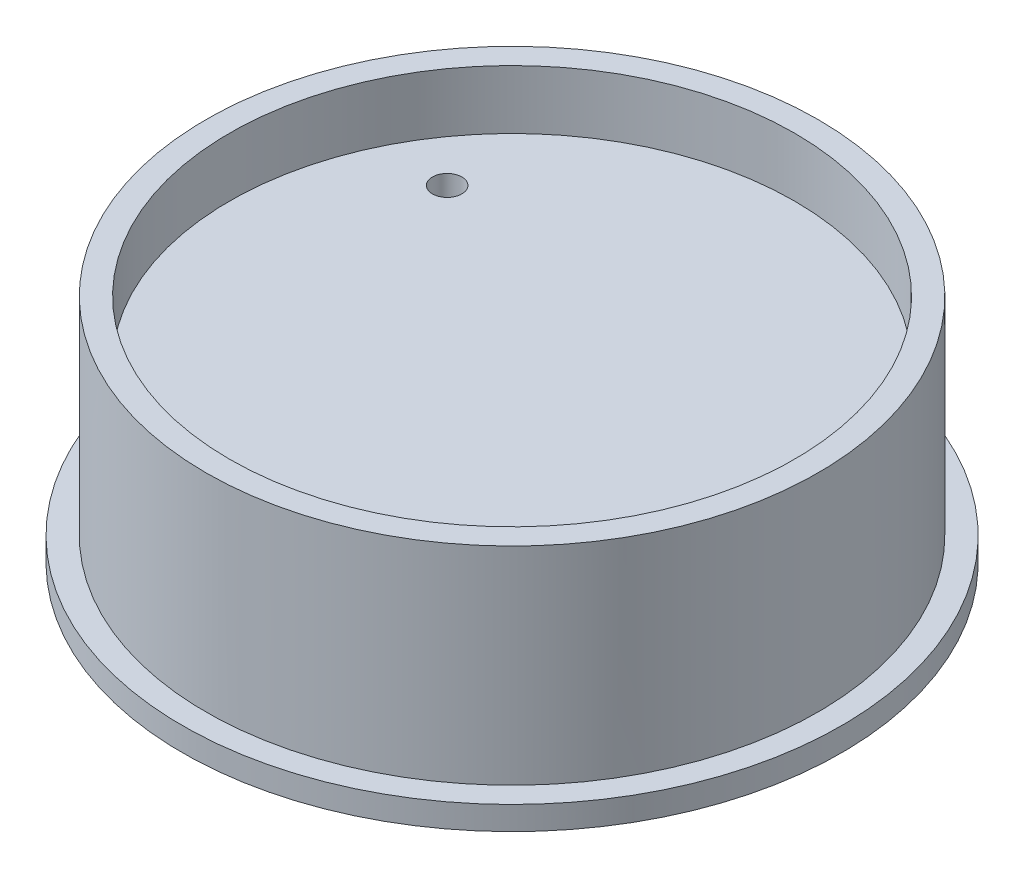
SolidWorks part; units mm, degrees
material "3.1355 (EN-AW 2024)"
ref_plane "Спереди" through (0, 0, 0) normal (0, 0, 1) x (1, 0, 0)
ref_plane "Сверху" through (0, 0, 0) normal (0, 1, 0) x (1, 0, 0)
ref_plane "Справа" through (0, 0, 0) normal (1, 0, 0) x (0, 0, -1)
sketch "Эскиз1" plane through (0, 0, 0) normal (0, 1, 0) x (1, 0, 0)
  circle A0 centre (0, 0) radius 26
  circle A1 centre (0, 0) radius 24
  dimension "D1" = 48
  dimension "D2" = 52
extrude "Бобышка-Вытянуть1" add sketch "Эскиз1" along normal blind 12.6
sketch "Эскиз2" plane through (0, 0, 0) normal (0, -1, 0) x (1, 0, 0)
  circle A1 centre (0, 0) radius 26 construction
  circle A2 centre (0, 0) radius 26
  circle A3 centre (0, 0) radius 28
  dimension "D1" = 2
extrude "Бобышка-Вытянуть2" add sketch "Эскиз2" against normal blind 2
sketch "Эскиз3" plane through (0, 12.6, 0) normal (0, 1, 0) x (1, 0, 0)
  circle A0 centre (0, 0) radius 26 construction
  circle A1 centre (0, 0) radius 26
extrude "Бобышка-Вытянуть3" add sketch "Эскиз3" along normal blind 2
sketch "Эскиз4" plane through (0, 14.6, 0) normal (0, 1, 0) x (1, 0, 0)
  circle A0 centre (0, 0) radius 26 construction
  circle A1 centre (0, 0) radius 26
  circle A2 centre (0, 0) radius 24 construction
  circle A3 centre (0, 0) radius 24
extrude "Бобышка-Вытянуть4" add sketch "Эскиз4" along normal blind 5
sketch "Эскиз5" plane through (0, 12.6, 0) normal (0, -1, 0) x (1, 0, 0)
  line L0 (0, 0) -> (13.1267, -20.0921) construction
  line L1 (0, 0) -> (20.0921, 13.1267) construction
  line L2 (-2.784, 0.379) -> (-3.6044, 1.6348) construction
  line L3 (-2.784, 0.379) -> (-3.6044, 1.6348) construction
  line L4 (13.9919, 13.322) -> (17.963, 15.9164)
  line L5 (17.8205, 7.4618) -> (21.7916, 10.0562)
  line L6 (-13.9919, -13.322) -> (-17.963, -15.9164)
  line L7 (-17.8205, -7.4618) -> (-21.7916, -10.0562)
  circle A0 centre (0, 0) radius 24 construction
  arc A1 (13.9919, 13.322) -> (17.8205, 7.4618) centre (15.9062, 10.3919) ccw
  arc A2 (21.7916, 10.0562) -> (17.963, 15.9164) centre (0, 0) ccw
  arc A3 (-17.8205, -7.4618) -> (-13.9919, -13.322) centre (-15.9062, -10.3919) cw
  arc A4 (-17.963, -15.9164) -> (-21.7916, -10.0562) centre (0, 0) cw
  dimension "D1" = 7
  dimension "D2" = 5
extrude "Бобышка-Вытянуть5" add sketch "Эскиз5" along normal blind 11
hole_wizard "Отверстие обработанное метчиком M3x0.51" positions "Эскиз7" profile "Эскиз6" tap size "M3x0.5" standard "Ansi Metric" end condition through all
sketch "Эскиз7" plane through (0, 1.6, 0) normal (0, -1, 0) x (-1, 0, 0)
  point P0 (-15.9062, -10.3919)
  point P3 (15.9062, 10.3919)
sketch "Эскиз6" plane through (15.9062, 1.6, 10.3919) normal (1, 0, 0) x (0, 0, -1)
  line L0 (0, 0) -> (0, 18)
  line L1 (0, 18) -> (1.25, 18)
  line L2 (1.25, 18) -> (1.25, 0)
  line L5 (1.25, 0) -> (0, 0)
  line L11 (0, -6.35) -> (0, 107.95) construction
  dimension "Диаметр проходного сверла" = 2.5
  dimension "Глубина проходного сверла" = 18
cosmetic thread "Отверстие резьбы1" parameters "D2"=3
cosmetic thread "Отверстие резьбы2" parameters "D2"=3
